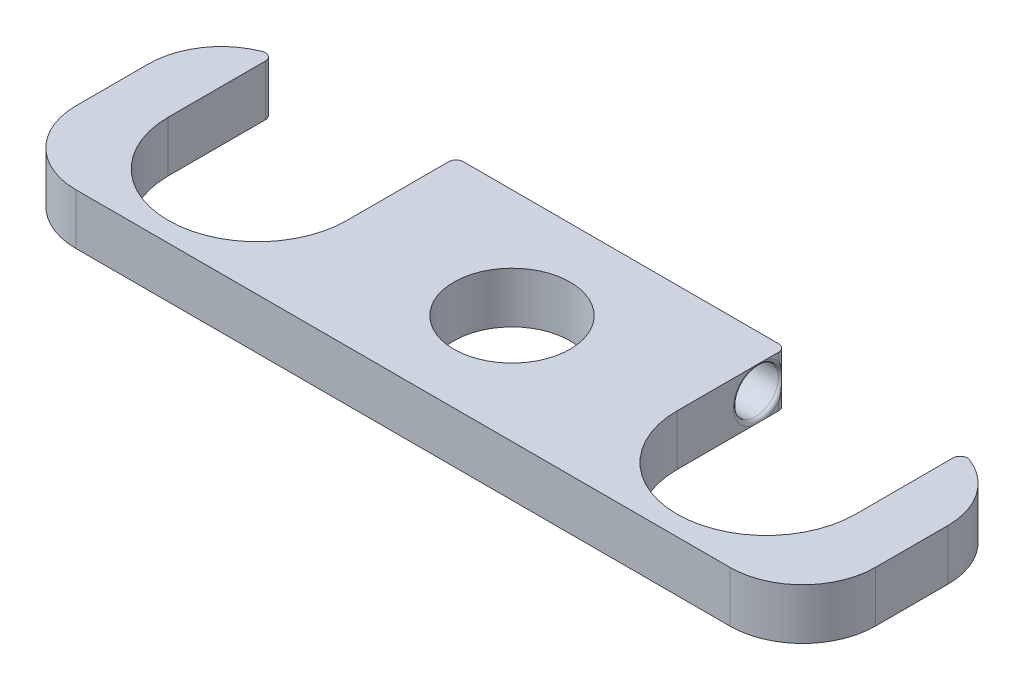
SolidWorks part; units mm, degrees
material "PLA"
ref_plane "Front Plane" through (0, 0, 0) normal (0, 0, 1) x (1, 0, 0)
ref_plane "Top Plane" through (0, 0, 0) normal (0, 1, 0) x (1, 0, 0)
ref_plane "Right Plane" through (0, 0, 0) normal (1, 0, 0) x (0, 0, -1)
sketch "Sketch1" plane through (0, 0, 0) normal (0, 1, 0) x (1, 0, 0)
  line L0 (0, 15) -> (0, -15) construction
  line L1 (-45, -15) -> (45, -15)
  line L2 (-55, -5) -> (-55, 5)
  line L3 (-45, 15) -> (45, 15)
  line L4 (55, -5) -> (55, 5)
  line L5 (-55, 0) -> (55, 0) construction
  line L7 (-55, 15) -> (0, 15) construction
  line L8 (0, 15) -> (-27.5, 15) construction
  circle A0 centre (0, 0) radius 8
  arc A2 (45, 15) -> (55, 5) centre (45, 5) cw
  arc A3 (45, -15) -> (55, -5) centre (45, -5) ccw
  arc A4 (-45, -15) -> (-55, -5) centre (-45, -5) cw
  arc A5 (-55, 5) -> (-45, 15) centre (-45, 5) cw
  point P0 (0, 0)
  point P17 (55, -15)
  point P20 (-55, -15)
  dimension "D3" = 16
  dimension "D5" = 10
  dimension "D1" = 30
  dimension "D2" = 110
extrude "Boss-Extrude1" add sketch "Sketch1" along normal blind 7
sketch "Sketch2" plane through (0, 7, 0) normal (0, 1, 0) x (1, 0, 0)
  line L1 (-22.7, 0) -> (-22.7, 15)
  line L2 (45, 15) -> (-45, 15) construction
  line L7 (-47.3, 0) -> (-47.3, 15)
  line L9 (-14.25, 0) -> (-22.7, 0) construction
  line L10 (-55, 0) -> (55, 0) construction
  line L11 (-55, 5) -> (-55, -5) construction
  line L12 (55, -5) -> (55, 5) construction
  line L13 (-47.3, 15) -> (-22.7, 15)
  circle A0 centre (-35, 0) radius 12.3 construction
  circle A1 centre (0, 0) radius 14.25 construction
  arc A3 (-47.3, 0) -> (-22.7, 0) centre (-35, 0) ccw
  dimension "D1" = 24.6
  dimension "D2" = 28.5
  dimension "D3" = 8.45
ref_axis "Axis1" through (0, 0, 0) along (0, 1, 0)
ref_plane "Plane1" through (0, 0, 0) normal (-1, 0, 0) x (0, 1, 0)
extrude "Cut-Extrude1" cut sketch "Sketch2" against normal blind 10
sketch "Sketch3" plane through (-22.7, 0, 0) normal (-1, 0, 0) x (0, 0, 1)
  line L0 (-15, 3.5) -> (0, 3.5) construction
  line L1 (-15, 0) -> (-15, 7) construction
  line L2 (0, 0) -> (0, 37.6258) construction
  line L3 (0, 3.5) -> (-11.3487, 7) construction
  line L4 (0, 7) -> (-15, 7) construction
  line L5 (-11.3487, 7) -> (-11.3487, 0) construction
  line L6 (-15, 0) -> (0, 0) construction
  circle A0 centre (-11.3487, 3.5) radius 3.1
  dimension "D1" = 6.2
extrude "Cut-Extrude2" cut sketch "Sketch3" against normal blind 6
fillet "Fillet1" radius 0.5 1 edges at (-22.7, 3.5, -8.2487) type face fillet first side face at (-16.7, 3.5, -8.2487) second side face at (-22.7, 3.5, -8.2487)
fillet "Fillet2" radius 1 1 edges at (-47.3, 3.5, -14.7319) type face fillet first side face at (-47.3, 3.5, -7.366) second side face at (-51.9961, 3.5, -10.5354)
fillet "Fillet3" radius 1 1 edges at (-22.7, 3.5, -15) type face fillet first side face at (-22.7, 3.5, -14.285) second side face at (11.15, 3.5, -15)
mirror "Mirror5" about plane through (0, 0, 0) normal (-1, 0, 0) of "Cut-Extrude2", "Cut-Extrude1"
fillet "Fillet5" radius 1 1 edges at (47.3, 3.5, -14.7319) type face fillet first side face at (47.3, 3.5, -7.366) second side face at (51.9961, 3.5, -10.5354)
fillet "Fillet6" radius 0.5 1 edges at (22.7, 3.5, -8.2487) type face fillet first side face at (16.7, 3.5, -8.2487) second side face at (22.7, 3.5, -8.2487)
fillet "Fillet7" radius 1 1 edges at (22.7, 3.5, -15) type face fillet first side face at (22.7, 3.5, -14.285) second side face at (0.5, 3.5, -15)
